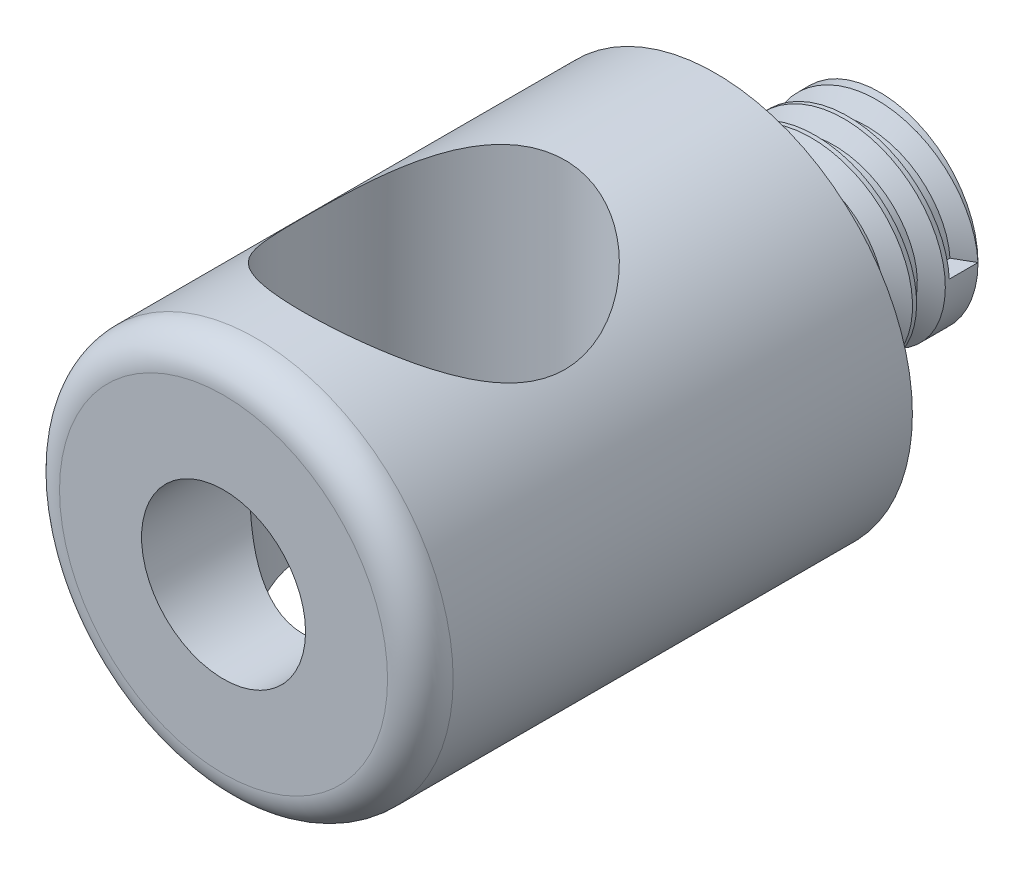
SolidWorks part; units mm, degrees
material "1.4000 (X6Cr13)"
ref_plane "Alzado" through (0, 0, 0) normal (0, 0, 1) x (1, 0, 0)
ref_plane "Planta" through (0, 0, 0) normal (0, 1, 0) x (1, 0, 0)
ref_plane "Vista lateral" through (0, 0, 0) normal (1, 0, 0) x (0, 0, -1)
sketch "Croquis1" plane through (0, 0, 0) normal (0, 0, 1) x (1, 0, 0)
  circle A0 centre (0, 0) radius 6
  dimension "D1" = 12
extrude "Saliente-Extruir1" add sketch "Croquis1" along normal blind 15
sketch "Croquis2" plane through (0, 0, 0) normal (0, 1, 0) x (1, 0, 0)
  line L0 (6, 0) -> (-6, 0) construction
  circle A0 centre (0, -8.59) radius 4
  dimension "D1" = 8
  dimension "D2" = 8.59
extrude "Cortar-Extruir1" cut sketch "Croquis2" against normal mid plane 15 contours A0
sketch "Croquis3" plane through (0, 0, 0) normal (0, 0, -1) x (-1, 0, 0)
  circle A0 centre (0, 0) radius 3
extrude "Saliente-Extruir2" add sketch "Croquis3" along normal blind 5
sketch "Croquis4" plane through (0, 0, 15) normal (0, 0, 1) x (1, 0, 0)
  circle A0 centre (0, 0) radius 2.5
  dimension "D1" = 5
extrude "Cortar-Extruir2" cut sketch "Croquis4" against normal up to surface (3.2875 mm away) up to face at (0.5473, 5.975, 4.6276)
fillet "Redondeo1" radius 1 1 edges at (6, 0, 15)
thread "Rosca1" pitch 1 method cut profile "Perfil de rosca1" start angle 0, offset 0, length 5, pitch 1, diameter 6
ref_plane "Plano1" through (3, 0, -5) normal (0, -1, 0) x (1, 0, 0)
sketch "Perfil de rosca1" plane through (3, 0, -5) normal (0, -1, 0) x (1, 0, 0)
  line L0 (0, 0) -> (0, 1) construction
  line L11 (0, 0) -> (0, 0.875)
  line L12 (0, 0.875) -> (-0.5413, 0.5625)
  line L13 (-0.5413, 0.5625) -> (-0.5413, 0.3125)
  line L15 (-0.5413, 0.3125) -> (0, 0)
  line L17 (-0.5413, 0.4375) -> (0, 0.4375) construction
  point P2 (0, 0)
  dimension "Pitch" = 1
  dimension "Profile_Angle" = 60
  dimension "Profile_Land" = 0.25
  dimension "Profile_Height" = 0.5413
